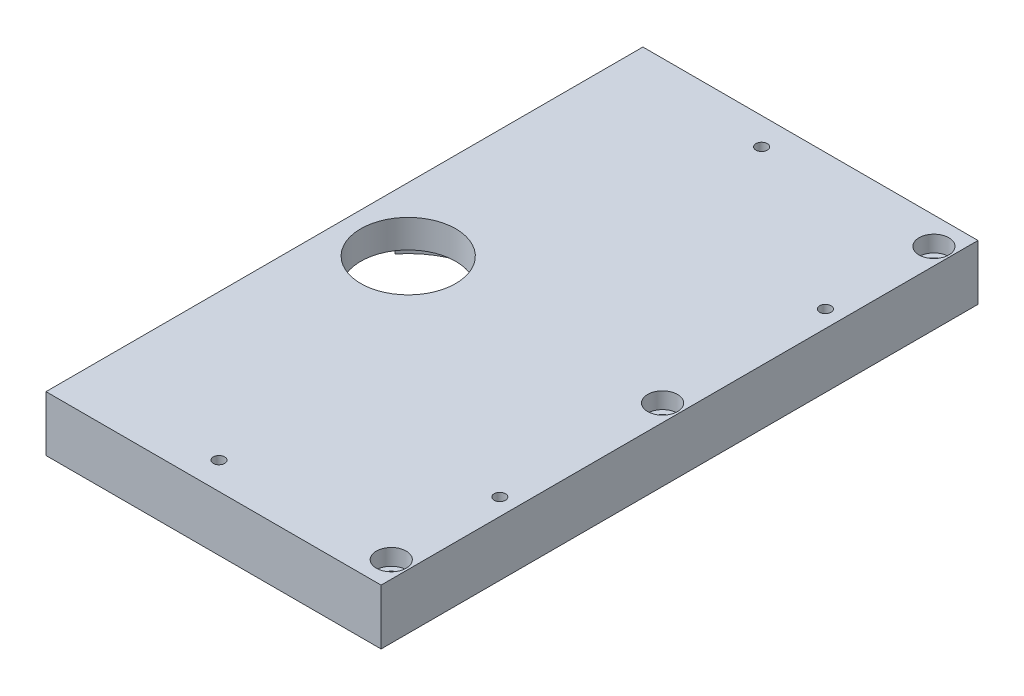
SolidWorks part; units mm, degrees
ref_plane "Front Plane" through (0, 0, 0) normal (0, 0, 1) x (1, 0, 0)
ref_plane "Top Plane" through (0, 0, 0) normal (0, 1, 0) x (1, 0, 0)
ref_plane "Right Plane" through (0, 0, 0) normal (1, 0, 0) x (0, 0, -1)
sketch "Sketch1" plane through (0, 0, 0) normal (0, 1, 0) x (1, 0, 0)
  line L1 (0, 0) -> (123.5, 0)
  line L2 (0, 0) -> (0, 220)
  line L3 (0, 220) -> (123.5, 220)
  line L4 (123.5, 0) -> (123.5, 220)
  dimension "D1" = 220
  dimension "D2" = 123.5
extrude "Bloco" add sketch "Sketch1" against normal blind 20.4
sketch "Sketch2" plane through (0, -20.4, 0) normal (0, -1, 0) x (-1, 0, 0)
  line L0 (-123.5, 110) -> (0, 110) construction
  line L1 (-123.5, 0) -> (-123.5, 220) construction
  line L2 (0, 220) -> (0, 0) construction
  line L3 (-23.5, 220) -> (-23.5, 0) construction
  line L4 (-123.5, 220) -> (0, 220) construction
  line L5 (0, 0) -> (-123.5, 0) construction
  line L6 (-123.5, 0) -> (-123.5, 220) construction
  circle A0 centre (-23.5, 110) radius 17.5
  circle A1 centre (-23.5, 110) radius 30
  dimension "D2" = 35
  dimension "D3" = 60
  dimension "D1" = 100
extrude "Furo Ø35 Passante" cut sketch "Sketch2" against normal through all contours A0 region at (23.5, -20.4, -110)
extrude "Rebaixo Ø60x10" cut sketch "Sketch2<4>" against normal blind 10
sketch "Sketch2<4>" plane through (0, -20.4, 0) normal (0, -1, 0) x (-1, 0, 0) same geometry as "Sketch2"
sketch "Posição Furos" plane through (0, 0, 0) normal (0, 1, 0) x (1, 0, 0)
  line L0 (117.25, 0) -> (117.25, 220) construction
  line L1 (0, 0) -> (123.5, 0) construction
  line L2 (123.5, 220) -> (0, 220) construction
  line L3 (117.25, 110) -> (23.5, 110) construction
  line L4 (123.5, 0) -> (123.5, 220) construction
  line L5 (117.25, 10) -> (0, 10) construction
  line L6 (0, 220) -> (0, 0) construction
  line L7 (117.25, 210) -> (0, 210) construction
  circle A0 centre (117.25, 10) radius 3.3
  circle A2 centre (117.25, 110) radius 3.3
  circle A3 centre (117.25, 50) radius 2.5
  circle A5 centre (53.75, 10) radius 2.5
  circle A6 centre (117.25, 170) radius 2.5
  circle A7 centre (117.25, 210) radius 3.3
  circle A8 centre (53.75, 210) radius 2.5
  dimension "D2" = 6.6
  dimension "D3" = 5
  dimension "D4" = 100
  dimension "D7" = 60
  dimension "D8" = 63.5
  dimension "D1" = 6.25
hole_wizard "Rebaixo M6 - Passante" positions "Sketch5" profile "Sketch6" counterbore size "M6" standard "ANSI Metric" end condition through all
sketch "Sketch5" plane through (0, 0, 0) normal (0, 1, 0) x (1, 0, 0)
  point P0 (117.25, 10)
  point P3 (117.25, 110)
  point P6 (117.25, 210)
sketch "Sketch6" plane through (117.25, 0, -10) normal (1, 0, 0) x (0, 0, 1)
  line L0 (0, 0) -> (0, 20.4)
  line L1 (0, 20.4) -> (3.3, 20.4)
  line L3 (3.3, 20.4) -> (3.3, 6)
  line L4 (3.3, 6) -> (5.5, 6)
  line L5 (5.5, 6) -> (5.5, 0)
  line L7 (5.5, 0) -> (0, 0)
  line L11 (0, -6.35) -> (0, 107.95) construction
  dimension "Thru Hole Dia." = 6.6
  dimension "Thru Hole Depth" = 20.4
  dimension "C'Bore Dia." = 11
  dimension "C'Bore Depth" = 6
hole_wizard "Furo M5x0.8 - Passante" positions "Sketch7" profile "Sketch8" tap size "M5x0.8" standard "ANSI Metric" end condition through all
sketch "Sketch7" plane through (0, 0, 0) normal (0, 1, 0) x (1, 0, 0)
  point P0 (53.75, 10)
  point P3 (117.25, 50)
  point P6 (117.25, 170)
  point P9 (53.75, 210)
sketch "Sketch8" plane through (53.75, 0, -10) normal (1, 0, 0) x (0, 0, 1)
  line L0 (0, 0) -> (0, 20.4)
  line L1 (0, 20.4) -> (2.1, 20.4)
  line L2 (2.1, 20.4) -> (2.1, 0)
  line L5 (2.1, 0) -> (0, 0)
  line L11 (0, -6.35) -> (0, 107.95) construction
  dimension "Thru Tap Drill Dia." = 4.2
  dimension "Thru Tap Drill Depth" = 20.4
cosmetic thread "Hole Thread1" parameters "D2"=5
cosmetic thread "Hole Thread2" parameters "D2"=5
cosmetic thread "Hole Thread3" parameters "D2"=5
cosmetic thread "Hole Thread4" parameters "D2"=5
